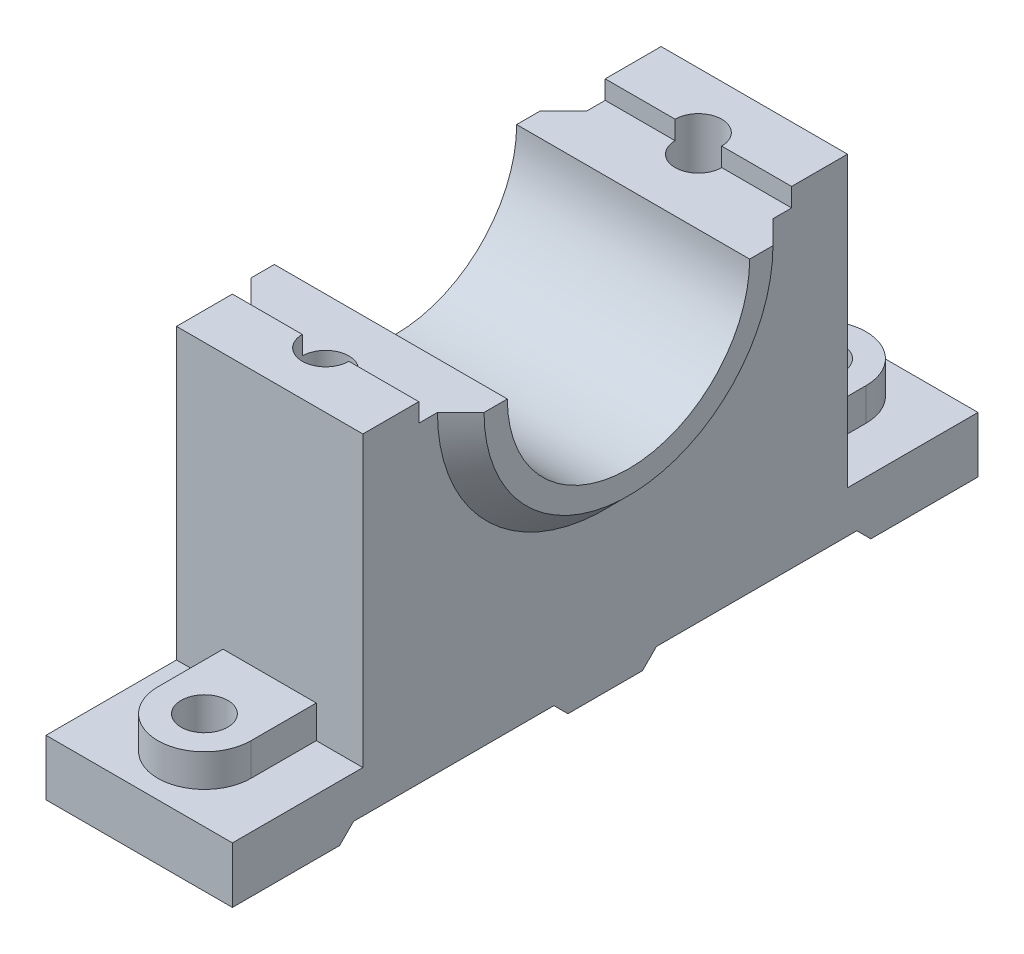
SolidWorks part; units mm, degrees
ref_plane "Front Plane" through (0, 0, 0) normal (0, 0, 1) x (1, 0, 0)
ref_plane "Top Plane" through (0, 0, 0) normal (0, 1, 0) x (1, 0, 0)
ref_plane "Right Plane" through (0, 0, 0) normal (1, 0, 0) x (0, 0, -1)
sketch "Sketch1" plane through (0, 0, 0) normal (1, 0, 0) x (0, 0, -1)
  line L0 (-40, -3) -> (-28.5, -3)
  line L2 (-40, -3) -> (-40, 3)
  line L3 (-40, 3) -> (40, 3)
  line L4 (40, -3) -> (40, 3)
  line L5 (-28.5, -3) -> (-27, -1.5)
  line L6 (-27, -1.5) -> (-5.5, -1.5)
  line L7 (-5.5, -1.5) -> (-4, -3)
  line L10 (-28.5, -3) -> (-4, -3) construction
  line L11 (0, 0) -> (0, 11.3399) construction
  line L12 (28.5, -3) -> (4, -3) construction
  line L13 (27, -1.5) -> (5.5, -1.5)
  line L14 (28.5, -3) -> (27, -1.5)
  line L15 (40, -3) -> (28.5, -3)
  line L16 (5.5, -1.5) -> (4, -3)
  line L17 (-4, -3) -> (4, -3)
  point P0 (0, 0)
  point P12 (5.5, -1.5)
  point P17 (-16.25, -3)
  dimension "D1" = 6
  dimension "D2" = 11.5
  dimension "D3" = 45
  dimension "D4" = 24.5
  dimension "D5" = 8
  dimension "D6" = 1.5
  dimension "D7" = 1.5
extrude "Boss-Extrude1" add sketch "Sketch1" along normal mid plane 20
sketch "Sketch2" plane through (10, 0, 0) normal (1, 0, 0) x (0, 0, -1)
  line L0 (0, -3) -> (0, 32) construction
  line L1 (-4, -3) -> (4, -3) construction
  line L2 (20, 32) -> (13, 32)
  line L3 (-13, 32) -> (-20, 32)
  line L4 (26, 34) -> (20, 34)
  line L5 (-20, 32) -> (-20, 34)
  line L6 (20, 32) -> (20, 34)
  line L7 (-20, 34) -> (-26, 34)
  line L8 (-26, 34) -> (-26, 3)
  line L9 (40, 3) -> (-40, 3) construction
  line L10 (26, 34) -> (26, 3)
  line L11 (-26, 3) -> (26, 3)
  line L12 (-13, 32) -> (13, 32)
  point P8 (0, 32)
  dimension "D1" = 35
  dimension "D2" = 40
  dimension "D3" = 2
  dimension "D5" = 6
  dimension "D6" = 20
  dimension "D7" = 6
extrude "Boss-Extrude2" add sketch "Sketch2" against normal blind 20
sketch "Sketch3" plane through (0, 3, 0) normal (0, 1, 0) x (1, 0, 0)
  line L0 (0, -33) -> (0, 33) construction
  line L1 (-5, -33) -> (-5, -25)
  line L2 (-5, -25) -> (5, -25)
  line L3 (5, -25) -> (5, -33)
  line L4 (-11, 0) -> (11, 0) construction
  line L5 (5, 25) -> (5, 33)
  line L6 (-5, 25) -> (5, 25)
  line L7 (-5, 33) -> (-5, 25)
  arc A0 (-5, -33) -> (5, -33) centre (0, -33) ccw
  circle A1 centre (0, -33) radius 2.5
  circle A2 centre (0, 33) radius 2.5
  arc A3 (-5, 33) -> (5, 33) centre (0, 33) cw
  point P4 (0, 0)
  dimension "D2" = 5
  dimension "D3" = 10
  dimension "D1" = 66
  dimension "D4" = 8
extrude "Boss-Extrude4" add sketch "Sketch3" along normal blind 3.5
sketch "Sketch5" plane through (0, 3, 0) normal (0, 1, 0) x (1, 0, 0)
  circle A0 centre (0, 33) radius 2.5 construction
  circle A1 centre (0, -33) radius 2.5 construction
  circle A2 centre (0, 33) radius 2.5
  circle A3 centre (0, -33) radius 2.5
extrude "Cut-Extrude2" cut sketch "Sketch5" against normal through all
sketch "Sketch6" plane through (10, 0, 0) normal (1, 0, 0) x (0, 0, -1)
  line L0 (20, 32) -> (-20, 32) construction
  circle A0 centre (0, 32) radius 13
  dimension "D1" = 26
extrude "Cut-Extrude3" cut sketch "Sketch6" against normal through all
sketch "Sketch8" plane through (10, 0, 0) normal (1, 0, 0) x (0, 0, -1)
  line L0 (-13, 32) -> (-15, 32)
  line L1 (13, 32) -> (15, 32)
  arc A0 (-13, 32) -> (13, 32) centre (0, 32) ccw construction
  arc A1 (-13, 32) -> (13, 32) centre (0, 32) ccw
  arc A2 (-15, 32) -> (15, 32) centre (0, 32) ccw
  dimension "D1" = 30
extrude "Boss-Extrude5" add sketch "Sketch8" along normal blind 2.5 and the other way blind 22.5
sketch "Sketch10" plane through (10, 0, 0) normal (1, 0, 0) x (0, 0, -1)
  line L0 (-18, 32) -> (-15, 32)
  line L1 (15, 32) -> (18, 32)
  arc A0 (-18, 32) -> (18, 32) centre (0, 32) ccw
  arc A1 (-15, 32) -> (15, 32) centre (0, 32) ccw
  dimension "D1" = 36
  dimension "D2" = 30
sketch "Sketch14" plane through (0, -1.5, 0) normal (0, -1, 0) x (1, 0, 0)
  line L0 (0, -20) -> (0, 20) construction
  circle A0 centre (0, -20) radius 6.5
  circle A1 centre (0, 20) radius 6.5
  point P4 (0, 0)
  dimension "D2" = 13
  dimension "D1" = 40
extrude "Cut-Extrude6" cut sketch "Sketch14" against normal blind 6
extrude "Boss-Extrude6" add sketch "Sketch10" along normal blind 2.5 and the other way blind 22.5
chamfer "Chamfer1" distance 2.5 angle 45 2 edges at (-12.5, 14, 0) (12.5, 14, 0)
sketch "Sketch15" plane through (0, 34, 0) normal (0, 1, 0) x (1, 0, 0)
  line L0 (-10, -20) -> (10, -20) construction
  line L1 (-10, 20) -> (10, 20) construction
  circle A0 centre (0, -20) radius 2.5
  circle A1 centre (0, 20) radius 2.5
  dimension "D1" = 5
extrude "Cut-Extrude7" cut sketch "Sketch15" against normal blind 30
